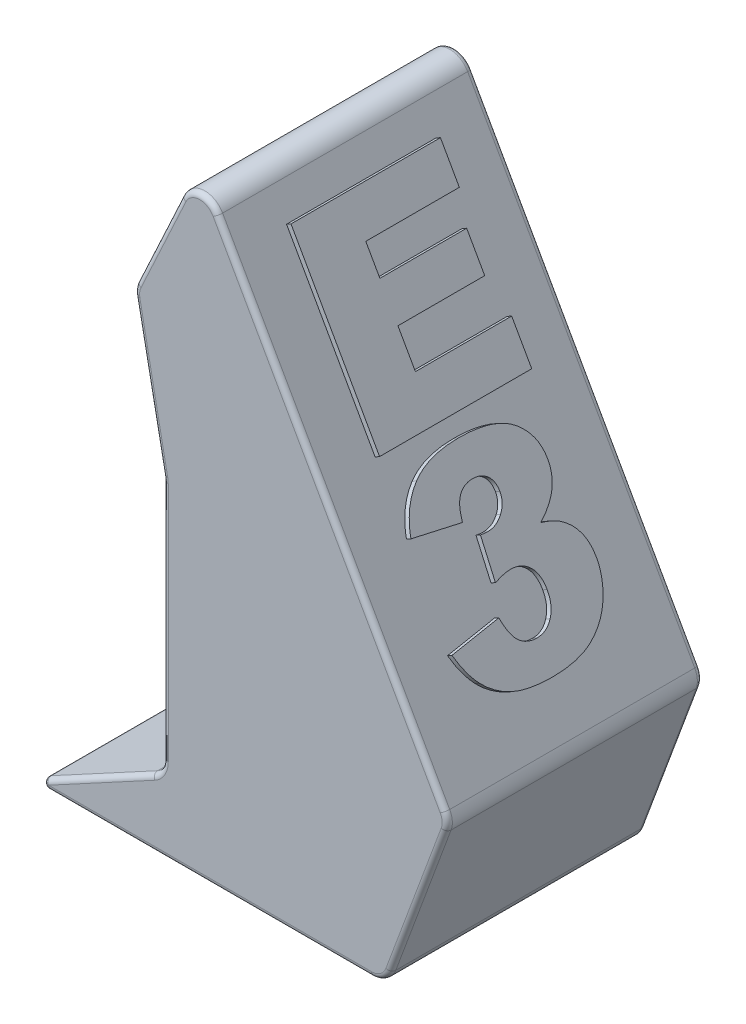
SolidWorks part; units mm, degrees
ref_plane "Alzado" through (0, 0, 0) normal (0, 0, 1) x (1, 0, 0)
ref_plane "Planta" through (0, 0, 0) normal (0, 1, 0) x (1, 0, 0)
ref_plane "Vista lateral" through (0, 0, 0) normal (1, 0, 0) x (0, 0, -1)
sketch "Sketch5" plane through (0, 0, 0) normal (0, 0, 1) x (1, 0, 0)
  line L0 (0, 0) -> (672.1713, 0)
  line L3 (740.3315, 484.8927) -> (370.4823, 1141.2206)
  line L5 (208.5032, 924.2833) -> (263.1478, 646.5009)
  line L6 (263.9, 638.7802) -> (263.9, 166.523)
  line L7 (242.9237, 131.3363) -> (0, 0)
  line L8 (299.3441, 1138.4064) -> (211.4608, 948.8271)
  line L9 (740.3315, 484.8927) -> (815.3488, 351.7684)
  line L10 (818.0053, 318.2236) -> (709.6757, 26.0924)
  arc A1 (815.3488, 351.7684) -> (818.0053, 318.2236) centre (780.5009, 332.1312) cw
  arc A2 (672.1713, 0) -> (709.6757, 26.0924) centre (672.1713, 40) ccw
  arc A3 (263.9, 166.523) -> (242.9237, 131.3363) centre (223.9, 166.523) cw
  arc A4 (263.1478, 646.5009) -> (263.9, 638.7802) centre (223.9, 638.7802) cw
  arc A5 (211.4608, 948.8271) -> (208.5032, 924.2833) centre (247.751, 932.0041) ccw
  arc A6 (370.4823, 1141.2206) -> (299.3441, 1138.4064) centre (335.6343, 1121.5833) ccw
  point P2 (207.1685, 936.9826)
  point P5 (0, 0)
  point P10 (0, 0)
  point P11 (0, 0)
  point P12 (0, 0)
  point P19 (577.6335, 773.6137)
  point P24 (700, 0)
  point P27 (263.9, 142.6772)
  point P30 (263.9, 642.6772)
  point P33 (205.9946, 937.0357)
  point P36 (332.1678, 1209.2127)
  dimension "D1" = 300
  dimension "D2" = 500
  dimension "D3" = 300
  dimension "D4" = 500
  dimension "D7" = 700
  dimension "D8" = 300
extrude "Boss-Extrude4" add sketch "Sketch5" along normal blind 250 and the other way blind 250
fillet "Fillet1" radius 10 13 edges at (258.258, 146.0406, 250) (263.9, 402.6516, 250) (263.7115, 642.6588, 250) (235.8255, 785.3921, 250) (208.0383, 936.7895, 250) (255.4024, 1043.6168, 250) (334.0532, 1161.552, 250) (592.9155, 746.4945, 250) (820.3761, 335.2889, 250) (763.8405, 172.158, 250) (695.0153, 7.1648, 250) (336.0857, 0, 250) (121.4618, 65.6682, 250)
fillet "Fillet2" radius 10 13 edges at (336.0857, 0, -250) (695.0153, 7.1648, -250) (763.8405, 172.158, -250) (820.3761, 335.2889, -250) (592.9155, 746.4945, -250) (334.0532, 1161.552, -250) (255.4024, 1043.6168, -250) (208.0383, 936.7895, -250) (235.8255, 785.3921, -250) (263.7115, 642.6588, -250) (263.9, 402.6516, -250) (258.258, 146.0406, -250) (121.4618, 65.6682, -250)
fillet "Fillet3" radius 10 3 edges at (11.576, 2.9289, -247.0711) (11.576, 2.9289, 247.0711) (0, 0, 0)
sketch "Sketch11" plane through (769.2894, 433.5046, 0) normal (0.8712, 0.4909, 0) x (0, 0, -1)
  line L0 (-144.2111, 752.5076) -> (148.552, 752.5076)
  line L1 (148.552, 752.5076) -> (148.552, 677.0259)
  line L2 (148.552, 677.0259) -> (-34.7264, 677.0259)
  line L3 (-34.7264, 677.0259) -> (-34.7264, 620.8366)
  line L4 (-34.7264, 620.8366) -> (135.2884, 620.8366)
  line L5 (135.2884, 620.8366) -> (135.2884, 548.731)
  line L6 (135.2884, 548.731) -> (-34.7264, 548.731)
  line L7 (-34.7264, 548.731) -> (-34.7264, 479.037)
  line L8 (-34.7264, 479.037) -> (153.8574, 479.037)
  line L9 (153.8574, 479.037) -> (153.8574, 398.9733)
  line L10 (153.8574, 398.9733) -> (-144.2111, 398.9733)
  line L11 (-144.2111, 398.9733) -> (-144.2111, 752.5076)
  line L12 (-51.3662, 257.3132) -> (-144.2111, 273.9529)
  line L13 (-149.5166, 99.3562) -> (-51.3662, 112.3786)
  line L14 (-35.2087, 158.6805) -> (-30.1445, 228.8568)
  spline S0 degree 3 poles (-144.2111, 273.9529) (-136.4942, 303.5347) (-121.7033, 326.2034) (-99.8385, 341.9589) knots 0 0 0 0 1 1 1 1
  spline S1 degree 3 poles (-99.8385, 341.9589) (-77.8129, 357.7144) (-46.7038, 365.5921) (-6.5112, 365.5921) knots 0 0 0 0 1 1 1 1
  spline S2 degree 3 poles (-6.5112, 365.5921) (39.6299, 365.5921) (72.9898, 356.9909) (93.5685, 339.7885) knots 0 0 0 0 1 1 1 1
  spline S3 degree 3 poles (93.5685, 339.7885) (114.1471, 322.586) (124.4364, 300.9624) (124.4364, 274.9176) knots 0 0 0 0 1 1 1 1
  spline S4 degree 3 poles (124.4364, 274.9176) (124.4364, 259.6444) (120.2564, 245.8181) (111.8963, 233.4388) knots 0 0 0 0 1 1 1 1
  spline S5 degree 3 poles (111.8963, 233.4388) (103.5362, 221.0594) (90.9157, 210.2074) (74.0348, 200.8828) knots 0 0 0 0 1 1 1 1
  spline S6 degree 3 poles (74.0348, 200.8828) (87.7003, 197.5066) (98.1504, 193.5677) (105.3851, 189.0661) knots 0 0 0 0 1 1 1 1
  spline S7 degree 3 poles (105.3851, 189.0661) (117.1213, 181.8314) (126.2048, 172.2656) (132.6357, 160.3686) knots 0 0 0 0 1 1 1 1
  spline S8 degree 3 poles (132.6357, 160.3686) (139.2273, 148.6323) (142.5231, 134.5649) (142.5231, 118.1663) knots 0 0 0 0 1 1 1 1
  spline S9 degree 3 poles (142.5231, 118.1663) (142.5231, 97.5877) (137.1373, 77.8129) (126.3656, 58.842) knots 0 0 0 0 1 1 1 1
  spline S10 degree 3 poles (126.3656, 58.842) (115.594, 40.0318) (100.0797, 25.4821) (79.8226, 15.1928) knots 0 0 0 0 1 1 1 1
  spline S11 degree 3 poles (79.8226, 15.1928) (59.5655, 5.0643) (32.9579, 0) (0, 0) knots 0 0 0 0 1 1 1 1
  spline S12 degree 3 poles (0, 0) (-32.1541, 0) (-57.5558, 3.7781) (-76.2052, 11.3343) knots 0 0 0 0 1 1 1 1
  spline S13 degree 3 poles (-76.2052, 11.3343) (-94.6938, 18.8905) (-109.967, 29.9033) (-122.0248, 44.3726) knots 0 0 0 0 1 1 1 1
  spline S14 degree 3 poles (-122.0248, 44.3726) (-133.9218, 59.0028) (-143.0858, 77.3306) (-149.5166, 99.3562) knots 0 0 0 0 1 1 1 1
  spline S15 degree 3 poles (-51.3662, 112.3786) (-47.5077, 92.6038) (-41.5592, 78.8579) (-33.5206, 71.141) knots 0 0 0 0 1 1 1 1
  spline S16 degree 3 poles (-33.5206, 71.141) (-25.3213, 63.5847) (-14.9516, 59.8066) (-2.4116, 59.8066) knots 0 0 0 0 1 1 1 1
  spline S17 degree 3 poles (-2.4116, 59.8066) (10.7716, 59.8066) (21.704, 64.6297) (30.3856, 74.276) knots 0 0 0 0 1 1 1 1
  spline S18 degree 3 poles (30.3856, 74.276) (39.228, 83.9222) (43.6492, 96.7838) (43.6492, 112.8609) knots 0 0 0 0 1 1 1 1
  spline S19 degree 3 poles (43.6492, 112.8609) (43.6492, 129.2595) (39.3888, 141.9604) (30.868, 150.9635) knots 0 0 0 0 1 1 1 1
  spline S20 degree 3 poles (30.868, 150.9635) (22.5079, 159.9666) (11.0932, 164.4682) (-3.3762, 164.4682) knots 0 0 0 0 1 1 1 1
  spline S21 degree 3 poles (-3.3762, 164.4682) (-11.0931, 164.4682) (-21.704, 162.539) (-35.2087, 158.6805) knots 0 0 0 0 1 1 1 1
  spline S22 degree 3 poles (-30.1445, 228.8568) (-24.6783, 228.0529) (-20.4178, 227.651) (-17.3632, 227.651) knots 0 0 0 0 1 1 1 1
  spline S23 degree 3 poles (-17.3632, 227.651) (-4.5015, 227.651) (6.1897, 231.7507) (14.7105, 239.95) knots 0 0 0 0 1 1 1 1
  spline S24 degree 3 poles (14.7105, 239.95) (23.3921, 248.1493) (27.7329, 257.8759) (27.7329, 269.1298) knots 0 0 0 0 1 1 1 1
  spline S25 degree 3 poles (27.7329, 269.1298) (27.7329, 279.9015) (24.5175, 288.5027) (18.0867, 294.9335) knots 0 0 0 0 1 1 1 1
  spline S26 degree 3 poles (18.0867, 294.9335) (11.6559, 301.3643) (2.8135, 304.5797) (-8.4405, 304.5797) knots 0 0 0 0 1 1 1 1
  spline S27 degree 3 poles (-8.4405, 304.5797) (-20.0159, 304.5797) (-29.421, 301.0428) (-36.6557, 293.9689) knots 0 0 0 0 1 1 1 1
  spline S28 degree 3 poles (-36.6557, 293.9689) (-43.8903, 287.0557) (-48.7938, 274.8372) (-51.3662, 257.3132) knots 0 0 0 0 1 1 1 1
extrude "Cut-Extrude1" cut sketch "Sketch11" against normal blind 100
extrude "Boss-Extrude5" add sketch "Sketch11<2>" along normal blind 10
sketch "Sketch11<2>" plane through (769.2894, 433.5046, 0) normal (0.8712, 0.4909, 0) x (0, 0, -1) same geometry as "Sketch11"
